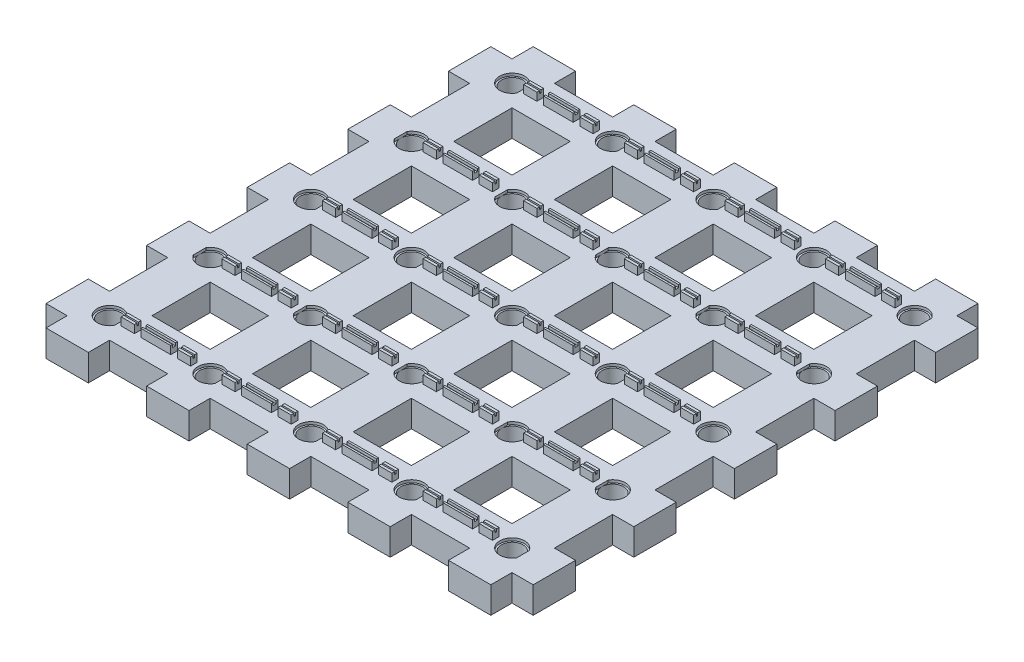
SolidWorks part; units mm, degrees
ref_plane "Front Plane" through (0, 0, 0) normal (0, 0, 1) x (1, 0, 0)
ref_plane "Top Plane" through (0, 0, 0) normal (0, 1, 0) x (1, 0, 0)
ref_plane "Right Plane" through (0, 0, 0) normal (1, 0, 0) x (0, 0, -1)
sketch "Sketch1" plane through (0, 0, 0) normal (0, 1, 0) x (1, 0, 0)
  line L1 (-110, -110) -> (110, -110)
  line L2 (-110, -110) -> (-110, 110)
  line L3 (-110, 110) -> (110, 110)
  line L4 (110, -110) -> (110, 110)
  line L5 (-110, -110) -> (110, 110) construction
  line L6 (-110, 110) -> (110, -110) construction
  point P0 (0, 0)
  dimension "D1" = 220
  dimension "D2" = 220
extrude "Boss-Extrude1" add sketch "Sketch1" along normal blind 10
sketch "Sketch2" plane through (0, 10, 0) normal (0, 1, 0) x (1, 0, 0)
  line L2 (-110, 110) -> (-110, -110) construction
  line L3 (-110, -110) -> (110, -110) construction
  circle A0 centre (-76, -75.925) radius 4.075
  circle A1 centre (-38, -75.925) radius 4.075
  circle A2 centre (0, -75.925) radius 4.075
  circle A3 centre (38, -75.925) radius 4.075
  circle A4 centre (76, -75.925) radius 4.075
  circle A5 centre (-76, -37.925) radius 4.075
  circle A6 centre (-38, -37.925) radius 4.075
  circle A7 centre (0, -37.925) radius 4.075
  circle A8 centre (38, -37.925) radius 4.075
  circle A9 centre (76, -37.925) radius 4.075
  circle A10 centre (-76, 0.075) radius 4.075
  circle A11 centre (-38, 0.075) radius 4.075
  circle A12 centre (0, 0.075) radius 4.075
  circle A13 centre (38, 0.075) radius 4.075
  circle A14 centre (76, 0.075) radius 4.075
  circle A15 centre (-76, 38.075) radius 4.075
  circle A16 centre (-38, 38.075) radius 4.075
  circle A17 centre (0, 38.075) radius 4.075
  circle A18 centre (38, 38.075) radius 4.075
  circle A19 centre (76, 38.075) radius 4.075
  circle A20 centre (-76, 76.075) radius 4.075
  circle A21 centre (-38, 76.075) radius 4.075
  circle A22 centre (0, 76.075) radius 4.075
  circle A23 centre (38, 76.075) radius 4.075
  circle A24 centre (76, 76.075) radius 4.075
  point P15 (0, 0)
  point P55 (0, 0)
  point P56 (0, 0)
  point P57 (0, 0)
  point P58 (0.075, -75.925)
  point P59 (0, 0)
  point P60 (0, 0)
  point P61 (0, 0)
  point P62 (0, 0)
  point P63 (0, 0)
  dimension "D1" = 8.15
  dimension "D5" = 38
  dimension "D7" = 38
  dimension "D2" = 30
  dimension "D3" = 34
  dimension "D4" = 5
  dimension "D6" = 5
extrude "Cut-Extrude1" cut sketch "Sketch2" against normal blind 10
sketch "Sketch3" plane through (0, 10, 0) normal (0, 1, 0) x (1, 0, 0)
  line L0 (-71.925, -78.2669) -> (-71.925, -73.5831)
  line L5 (-80.075, -35.5831) -> (-80.075, -40.2669)
  line L10 (-71.925, -2.2669) -> (-71.925, 2.4169)
  line L11 (-80.075, 40.4169) -> (-80.075, 35.7331)
  line L12 (-71.925, 73.7331) -> (-71.925, 78.4169)
  line L13 (-33.925, 73.7331) -> (-33.925, 78.4169)
  line L14 (-42.075, 40.4169) -> (-42.075, 35.7331)
  line L15 (-33.925, -2.2669) -> (-33.925, 2.4169)
  line L16 (-33.925, -78.2669) -> (-33.925, -73.5831)
  line L17 (-42.075, -35.5831) -> (-42.075, -40.2669)
  line L18 (4.075, 73.7331) -> (4.075, 78.4169)
  line L19 (-4.075, 40.4169) -> (-4.075, 35.7331)
  line L20 (4.075, -2.2669) -> (4.075, 2.4169)
  line L21 (4.075, -78.2669) -> (4.075, -73.5831)
  line L22 (-4.075, -35.5831) -> (-4.075, -40.2669)
  line L23 (42.075, 73.7331) -> (42.075, 78.4169)
  line L24 (33.925, 40.4169) -> (33.925, 35.7331)
  line L25 (42.075, -2.2669) -> (42.075, 2.4169)
  line L26 (42.075, -78.2669) -> (42.075, -73.5831)
  line L27 (33.925, -35.5831) -> (33.925, -40.2669)
  line L28 (80.075, 73.7331) -> (80.075, 78.4169)
  line L29 (71.925, 40.4169) -> (71.925, 35.7331)
  line L30 (80.075, -2.2669) -> (80.075, 2.4169)
  line L31 (80.075, -78.2669) -> (80.075, -73.5831)
  line L32 (71.925, -35.5831) -> (71.925, -40.2669)
  arc A0 (-71.925, -73.5831) -> (-71.925, -78.2669) centre (-76, -75.925) ccw
  circle A1 centre (-76, -75.925) radius 4.075 construction
  arc A6 (-80.075, -40.2669) -> (-80.075, -35.5831) centre (-76, -37.925) ccw
  circle A7 centre (-76, -37.925) radius 4.075 construction
  arc A12 (-71.925, 2.4169) -> (-71.925, -2.2669) centre (-76, 0.075) ccw
  arc A13 (-80.075, 35.7331) -> (-80.075, 40.4169) centre (-76, 38.075) ccw
  circle A14 centre (-76, 0.075) radius 4.075 construction
  circle A15 centre (-76, 38.075) radius 4.075 construction
  arc A16 (-71.925, 78.4169) -> (-71.925, 73.7331) centre (-76, 76.075) ccw
  circle A17 centre (-76, 76.075) radius 4.075 construction
  arc A18 (-33.925, 78.4169) -> (-33.925, 73.7331) centre (-38, 76.075) ccw
  arc A19 (-42.075, 35.7331) -> (-42.075, 40.4169) centre (-38, 38.075) ccw
  arc A20 (-33.925, 2.4169) -> (-33.925, -2.2669) centre (-38, 0.075) ccw
  arc A21 (-33.925, -73.5831) -> (-33.925, -78.2669) centre (-38, -75.925) ccw
  arc A22 (-42.075, -40.2669) -> (-42.075, -35.5831) centre (-38, -37.925) ccw
  arc A23 (4.075, 78.4169) -> (4.075, 73.7331) centre (0, 76.075) ccw
  arc A24 (-4.075, 35.7331) -> (-4.075, 40.4169) centre (0, 38.075) ccw
  arc A25 (4.075, 2.4169) -> (4.075, -2.2669) centre (0, 0.075) ccw
  arc A26 (4.075, -73.5831) -> (4.075, -78.2669) centre (0, -75.925) ccw
  arc A27 (-4.075, -40.2669) -> (-4.075, -35.5831) centre (0, -37.925) ccw
  arc A28 (42.075, 78.4169) -> (42.075, 73.7331) centre (38, 76.075) ccw
  arc A29 (33.925, 35.7331) -> (33.925, 40.4169) centre (38, 38.075) ccw
  arc A30 (42.075, 2.4169) -> (42.075, -2.2669) centre (38, 0.075) ccw
  arc A31 (42.075, -73.5831) -> (42.075, -78.2669) centre (38, -75.925) ccw
  arc A32 (33.925, -40.2669) -> (33.925, -35.5831) centre (38, -37.925) ccw
  arc A33 (80.075, 78.4169) -> (80.075, 73.7331) centre (76, 76.075) ccw
  arc A34 (71.925, 35.7331) -> (71.925, 40.4169) centre (76, 38.075) ccw
  arc A35 (80.075, 2.4169) -> (80.075, -2.2669) centre (76, 0.075) ccw
  arc A36 (80.075, -73.5831) -> (80.075, -78.2669) centre (76, -75.925) ccw
  arc A37 (71.925, -40.2669) -> (71.925, -35.5831) centre (76, -37.925) ccw
  point P0 (-76, -75.925)
  point P7 (-76, 76.075)
  point P11 (-76, 76.075)
  point P21 (-76, -37.925)
  point P26 (-76, -37.925)
  point P31 (-76, 38.075)
  point P51 (-76, 0.075)
  point P56 (-76, 38.075)
  point P60 (-76, 38.075)
  point P61 (-76, 0.075)
  point P102 (-38, -75.925)
  dimension "D1" = 4.7
  dimension "D3" = 4.7
  dimension "D5" = 4.7
  dimension "D6" = 4.7
  dimension "D2" = 4.7
extrude "Cut-Extrude2" cut sketch "Sketch3" against normal blind 1
sketch "Sketch4" plane through (0, 10, 0) normal (0, 1, 0) x (1, 0, 0)
  line L0 (-110, 110) -> (-110, -110) construction
  line L1 (-68, 46) -> (-46, 46)
  line L2 (-68, 46) -> (-68, 68)
  line L3 (-68, 68) -> (-46, 68)
  line L4 (-46, 46) -> (-46, 68)
  line L5 (-68, 46) -> (-46, 68) construction
  line L6 (-68, 68) -> (-46, 46) construction
  line L7 (110, 110) -> (-110, 110) construction
  line L8 (-30, 68) -> (-8, 68)
  line L9 (-30, 46) -> (-30, 68)
  line L10 (-30, 46) -> (-8, 46)
  line L11 (-8, 46) -> (-8, 68)
  line L12 (8, 68) -> (30, 68)
  line L13 (8, 46) -> (8, 68)
  line L14 (8, 46) -> (30, 46)
  line L15 (30, 46) -> (30, 68)
  line L16 (46, 68) -> (68, 68)
  line L17 (46, 46) -> (46, 68)
  line L18 (46, 46) -> (68, 46)
  line L19 (68, 46) -> (68, 68)
  line L20 (-30, 30) -> (-8, 30)
  line L21 (-30, 8) -> (-30, 30)
  line L22 (-30, 8) -> (-8, 8)
  line L23 (-8, 8) -> (-8, 30)
  line L24 (8, 30) -> (30, 30)
  line L25 (8, 8) -> (8, 30)
  line L26 (8, 8) -> (30, 8)
  line L27 (30, 8) -> (30, 30)
  line L28 (46, 30) -> (68, 30)
  line L29 (46, 8) -> (46, 30)
  line L30 (46, 8) -> (68, 8)
  line L31 (68, 8) -> (68, 30)
  line L32 (-68, 30) -> (-46, 30)
  line L33 (-68, 8) -> (-68, 30)
  line L34 (-68, 8) -> (-46, 8)
  line L35 (-46, 8) -> (-46, 30)
  line L36 (-30, -8) -> (-8, -8)
  line L37 (-30, -30) -> (-30, -8)
  line L38 (-30, -30) -> (-8, -30)
  line L39 (-8, -30) -> (-8, -8)
  line L40 (8, -8) -> (30, -8)
  line L41 (8, -30) -> (8, -8)
  line L42 (8, -30) -> (30, -30)
  line L43 (30, -30) -> (30, -8)
  line L44 (46, -8) -> (68, -8)
  line L45 (46, -30) -> (46, -8)
  line L46 (46, -30) -> (68, -30)
  line L47 (68, -30) -> (68, -8)
  line L48 (-68, -8) -> (-46, -8)
  line L49 (-68, -30) -> (-68, -8)
  line L50 (-68, -30) -> (-46, -30)
  line L51 (-46, -30) -> (-46, -8)
  line L52 (-30, -46) -> (-8, -46)
  line L53 (-30, -68) -> (-30, -46)
  line L54 (-30, -68) -> (-8, -68)
  line L55 (-8, -68) -> (-8, -46)
  line L56 (8, -46) -> (30, -46)
  line L57 (8, -68) -> (8, -46)
  line L58 (8, -68) -> (30, -68)
  line L59 (30, -68) -> (30, -46)
  line L60 (46, -46) -> (68, -46)
  line L61 (46, -68) -> (46, -46)
  line L62 (46, -68) -> (68, -68)
  line L63 (68, -68) -> (68, -46)
  line L64 (-68, -46) -> (-46, -46)
  line L65 (-68, -68) -> (-68, -46)
  line L66 (-68, -68) -> (-46, -68)
  line L67 (-46, -68) -> (-46, -46)
  line L68 (-68, 84) -> (-68, 92)
  line L76 (-84, 68) -> (-84, 46)
  line L109 (-46, 84) -> (-68, 84)
  line L158 (-92, 84) -> (-92, 68)
  line L177 (-84, 92) -> (-68, 92)
  line L194 (-92, 84) -> (-84, 84)
  line L195 (-92, 68) -> (-84, 68)
  line L196 (-84, 84) -> (-84, 92)
  line L197 (-92, 46) -> (-84, 46)
  line L198 (-92, 30) -> (-84, 30)
  line L201 (-92, 46) -> (-92, 30)
  line L202 (-84, 30) -> (-84, 8)
  line L203 (-92, 8) -> (-84, 8)
  line L204 (-92, -8) -> (-84, -8)
  line L205 (-92, 8) -> (-92, -8)
  line L206 (-84, -8) -> (-84, -30)
  line L207 (-92, -30) -> (-84, -30)
  line L208 (-92, -46) -> (-84, -46)
  line L209 (-46, 84) -> (-46, 92)
  line L210 (-46, 92) -> (-30, 92)
  line L211 (-30, 84) -> (-30, 92)
  line L212 (-8, 84) -> (-30, 84)
  line L213 (-8, 84) -> (-8, 92)
  line L214 (-8, 92) -> (8, 92)
  line L215 (8, 84) -> (8, 92)
  line L216 (30, 84) -> (8, 84)
  line L217 (30, 84) -> (30, 92)
  line L218 (30, 92) -> (46, 92)
  line L219 (46, 84) -> (46, 92)
  line L220 (68, 84) -> (46, 84)
  line L221 (0, -5.5) -> (0, 5.5) construction
  line L222 (-92, -30) -> (-92, -46)
  line L223 (-84, -46) -> (-84, -68)
  line L224 (-92, -68) -> (-84, -68)
  line L225 (-92, -84) -> (-84, -84)
  line L226 (-92, -68) -> (-92, -84)
  line L227 (-5.5, 0) -> (5.5, 0) construction
  line L228 (84, -84) -> (84, -92)
  line L229 (68, -92) -> (84, -92)
  line L230 (68, -84) -> (68, -92)
  line L231 (84, -84) -> (84, -92)
  line L232 (68, -84) -> (46, -84)
  line L233 (46, -84) -> (46, -92)
  line L234 (84, 84) -> (84, 92)
  line L235 (30, -92) -> (46, -92)
  line L236 (30, -84) -> (30, -92)
  line L237 (30, -84) -> (8, -84)
  line L238 (8, -84) -> (8, -92)
  line L239 (68, 84) -> (68, 92)
  line L240 (68, 92) -> (84, 92)
  line L241 (84, 84) -> (84, 92)
  line L242 (-8, -92) -> (8, -92)
  line L243 (-8, -84) -> (-8, -92)
  line L244 (-8, -84) -> (-30, -84)
  line L245 (-30, -84) -> (-30, -92)
  line L246 (-46, -92) -> (-30, -92)
  line L247 (-46, -84) -> (-46, -92)
  line L248 (-84, -84) -> (-84, -92)
  line L249 (-84, -92) -> (-68, -92)
  line L250 (-46, -84) -> (-68, -84)
  line L251 (92, 84) -> (92, 68)
  line L252 (-92, 46) -> (-92, 30) [skipped]
  line L253 (-92, 30) -> (-84, 30) [skipped]
  line L254 (-84, 30) -> (-84, 8) [skipped]
  line L255 (-92, 8) -> (-84, 8) [skipped]
  line L256 (-92, 8) -> (-92, -8) [skipped]
  line L257 (-92, -8) -> (-84, -8) [skipped]
  line L258 (-84, -8) -> (-84, -30) [skipped]
  line L259 (-92, -30) -> (-84, -30) [skipped]
  line L260 (-92, -30) -> (-92, -46) [skipped]
  line L261 (-92, -46) -> (-84, -46) [skipped]
  line L262 (-84, -46) -> (-84, -68) [skipped]
  line L263 (-92, -106) -> (-84, -106) [skipped]
  line L264 (-84, -84) -> (-84, -106) [skipped]
  line L265 (-68, -84) -> (-68, -92)
  line L266 (92, 68) -> (84, 68)
  line L267 (84, 68) -> (84, 46)
  line L268 (92, 46) -> (84, 46)
  line L269 (92, 46) -> (92, 30)
  line L270 (92, 30) -> (84, 30)
  line L271 (92, 8) -> (84, 8)
  line L272 (84, 30) -> (84, 8)
  line L273 (92, 8) -> (92, -8)
  line L274 (92, -8) -> (84, -8)
  line L275 (84, -8) -> (84, -30)
  line L276 (92, -30) -> (84, -30)
  line L277 (92, -30) -> (92, -46)
  line L278 (92, -46) -> (84, -46)
  line L279 (84, -46) -> (84, -68)
  line L280 (92, -68) -> (84, -68)
  line L281 (92, -68) -> (92, -84)
  line L282 (92, -84) -> (84, -84)
  line L283 (84, 84) -> (92, 84)
  line L285 (-110, 110) -> (110, 110)
  line L286 (-110, 110) -> (-110, -110)
  line L287 (-110, -110) -> (110, -110)
  line L288 (110, 110) -> (110, -110)
  point P0 (-57, 57)
  dimension "D2" = 22
  dimension "D3" = 22
  dimension "D4" = 53
  dimension "D6" = 16
  dimension "D8" = 16
  dimension "D9" = 16
  dimension "D10" = 26
  dimension "D11" = 26
  dimension "D12" = 4
  dimension "D14" = 53
  dimension "D19" = 8
  dimension "D20" = 8
  dimension "D5" = 4
  dimension "D7" = 4
  dimension "D15" = 5
extrude "Cut-Extrude3" cut sketch "Sketch4" against normal through all contours L62 L63 L60 L61 | L58 L59 L56 L57 | L54 L55 L52 L53 | L66 L67 L64 L65 | L50 L51 L48 L49 | L38 L39 L36 L37 | L42 L43 L40 L41 | L46 L47 L44 L45 | L30 L31 L28 L29 | L26 L27 L24 L25 | L22 L23 L20 L21 | L34 L35 L32 L33 | L1 L4 L3 L2 | L10 L11 L8 L9 | L14 L15 L12 L13 | L18 L19 L16 L17 | L288 L285 L286 L287 L234 L283 L251 L266 L267 L268 L269 L270 L272 L271 L273 L274 L275 L276 L277 L278 L279 L280 L281 L282 L228 L229 L230 L232 L233 L235 L236 L237 L238 L242 L243 L244 L245 L246 L247 L250 L265 L249 L248 L225 L226 L224 L223 L208 L222 L207 region at (-57, 10, -57) region at (-19, 10, -57) region at (19, 10, -57) region at (57, 10, -57) region at (-19, 10, -19) region at (19, 10, -19) region at (57, 10, -19) region at (-57, 10, -19) region at (-19, 10, 19) region at (19, 10, 19) region at (57, 10, 19) region at (-57, 10, 19) region at (-19, 10, 57) region at (19, 10, 57) region at (57, 10, 57) region at (-57, 10, 57) region at (0, 10, -106.8887)
sketch "Sketch5" plane through (0, 10, 0) normal (0, 1, 0) x (1, 0, 0)
  line L0 (-76, 76.075) -> (92, 76) construction
  line L2 (-71.925, 73.7331) -> (-71.925, 78.4169) construction
  line L11 (-70.425, 74.8214) -> (-65.425, 74.8214)
  line L12 (-70.425, 74.8214) -> (-70.425, 77.3214)
  line L13 (-70.425, 77.3214) -> (-65.425, 77.3214)
  line L14 (-65.425, 74.8214) -> (-65.425, 77.3214)
  line L15 (-70.425, 74.8214) -> (-65.425, 77.3214) construction
  line L16 (-70.425, 77.3214) -> (-65.425, 74.8214) construction
  line L17 (92, 84) -> (92, 68) construction
  line L18 (-49.2, 74.8214) -> (-44.2, 74.8214)
  line L19 (-49.2, 74.8214) -> (-49.2, 77.3214)
  line L20 (-49.2, 77.3214) -> (-44.2, 77.3214)
  line L21 (-44.2, 74.8214) -> (-44.2, 77.3214)
  line L22 (-49.2, 74.8214) -> (-44.2, 77.3214) construction
  line L23 (-49.2, 77.3214) -> (-44.2, 74.8214) construction
  line L24 (-62.925, 74.8119) -> (-51.7, 74.8119)
  line L25 (-62.925, 74.8119) -> (-62.925, 77.3214)
  line L26 (-62.925, 77.3214) -> (-51.7, 77.3214)
  line L27 (-51.7, 74.8119) -> (-51.7, 77.3214)
  line L28 (-62.925, 74.8119) -> (-51.7, 77.3214) construction
  line L29 (-62.925, 77.3214) -> (-51.7, 74.8119) construction
  arc A0 (-33.925, 78.4169) -> (-33.925, 73.7331) centre (-38, 76.075) ccw construction
  point P4 (0, 0)
  point P5 (-67.925, 76.0714)
  point P12 (-46.7, 76.0714)
  point P20 (-57.3125, 76.0667)
  point P25 (-67.925, 76.075)
  point P26 (0, 0)
  point P28 (-67.925, 79.1857)
  dimension "D1" = 2.5
  dimension "D2" = 5
  dimension "D3" = 1.5
  dimension "D4" = 5
  dimension "D5" = 2.5
  dimension "D6" = 1.5
  dimension "D7" = 2.5
  dimension "D8" = 2.5
extrude "Boss-Extrude2" add sketch "Sketch5" along normal blind 3 contours L11 L14 L13 L12 | L24 L27 L26 L25 | L20 L21 L18 L19 region at (-67.925, 10, -76.0714) region at (-57.3125, 10, -76.0667)
sketch "Sketch6" plane through (0, 13, 0) normal (0, 1, 0) x (1, 0, 0)
  line L0 (-70.425, 76.0714) -> (-65.425, 76.0714) construction
  line L20 (-70.425, 77.3214) -> (-70.425, 74.8214) construction
  line L21 (-65.425, 74.8214) -> (-65.425, 77.3214) construction
  line L22 (-62.925, 76.0667) -> (-51.7, 76.0667) construction
  line L25 (-62.925, 74.8119) -> (-62.925, 77.3214) construction
  line L29 (-70.425, 75.7964) -> (-65.425, 75.7964)
  line L30 (-70.425, 75.7964) -> (-70.425, 76.3464)
  line L31 (-70.425, 76.3464) -> (-65.425, 76.3464)
  line L32 (-65.425, 75.7964) -> (-65.425, 76.3464)
  line L33 (-70.425, 75.7964) -> (-65.425, 76.3464) construction
  line L34 (-70.425, 76.3464) -> (-65.425, 75.7964) construction
  line L39 (-51.7, 74.8119) -> (-51.7, 77.3214) construction
  line L40 (-49.2, 76.0714) -> (-44.2, 76.0714) construction
  line L46 (-49.2, 74.8214) -> (-49.2, 77.3214) construction
  line L47 (-44.2, 74.8214) -> (-44.2, 77.3214) construction
  line L48 (-44.2, 74.8214) -> (-44.2, 77.3214) construction
  line L49 (-62.925, 75.5167) -> (-51.7, 75.5167)
  line L50 (-62.925, 75.5167) -> (-62.925, 76.6167)
  line L51 (-62.925, 76.6167) -> (-51.7, 76.6167)
  line L52 (-51.7, 75.5167) -> (-51.7, 76.6167)
  line L53 (-62.925, 75.5167) -> (-51.7, 76.6167) construction
  line L54 (-62.925, 76.6167) -> (-51.7, 75.5167) construction
  line L55 (-49.2, 75.7964) -> (-44.2, 75.7964)
  line L56 (-49.2, 75.7964) -> (-49.2, 76.3464)
  line L57 (-49.2, 76.3464) -> (-44.2, 76.3464)
  line L58 (-44.2, 75.7964) -> (-44.2, 76.3464)
  line L59 (-49.2, 75.7964) -> (-44.2, 76.3464) construction
  line L60 (-49.2, 76.3464) -> (-44.2, 75.7964) construction
  point P18 (-67.925, 76.0714)
  point P23 (-57.3125, 76.0667)
  point P28 (-46.7, 76.0714)
  dimension "D1" = 0.55
  dimension "D2" = 0.55
  dimension "D3" = 1.1
extrude "Cut-Extrude4" cut sketch "Sketch6" against normal blind 1
pattern_linear "LPattern1" count 5 spacing 38 along (0, 0, 1) of "Boss-Extrude2", "Cut-Extrude4"
pattern_linear "LPattern2" count 4 spacing 38 along (1, 0, 0) of "LPattern1"
